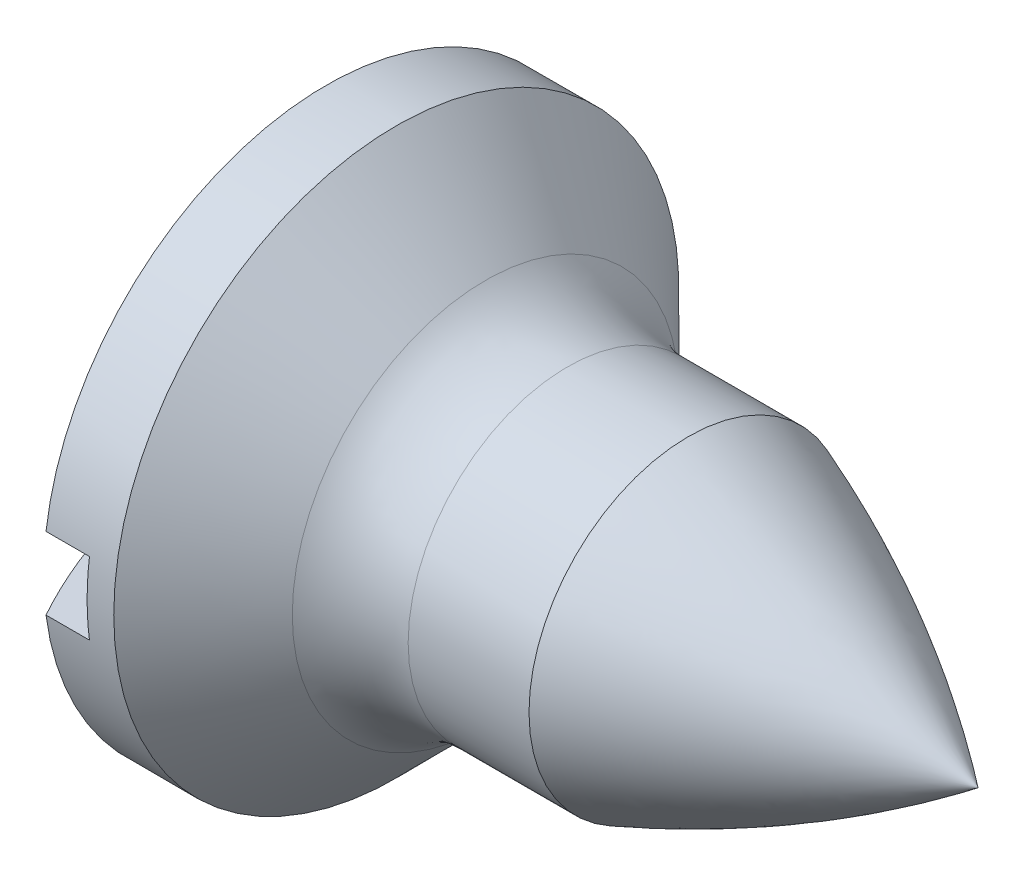
SolidWorks part; units mm, degrees
ref_plane "Front" through (0, 0, 0) normal (0, 0, 1) x (1, 0, 0)
ref_plane "Top" through (0, 0, 0) normal (0, 1, 0) x (1, 0, 0)
ref_plane "Right" through (0, 0, 0) normal (1, 0, 0) x (0, 0, -1)
sketch "Sketch1" plane through (0, 0, 0) normal (0, 0, 1) x (1, 0, 0)
  line L0 (-40.1945, 0) -> (11.3165, 0) construction
  line L1 (5.0078, 1.1) -> (5.0078, 0)
  line L2 (5.0078, 1.1) -> (2.1735, 1.1)
  line L3 (1.6078, 1.3343) -> (0.9916, 1.9506)
  line L4 (0.9916, 1.9506) -> (0.5078, 1.9506)
  line L5 (5.0078, 0) -> (0, 0)
  line L6 (2.4078, 2.2911) -> (2.4078, -1.7726) construction
  arc A0 (0.5078, 1.9506) -> (0, 0) centre (4, 0) ccw
  arc A1 (2.1735, 1.1) -> (1.6078, 1.3343) centre (2.1735, 1.9) cw
  point P12 (0.0078, 0.25)
  dimension "D2" = 45
  dimension "l" = 4.5
  dimension "k" = 1.1
  dimension "f" = 0.5
revolve "Base" add sketch "Sketch1" angle 360 about L0
cosmetic thread "ThreadCosmetic1" [suppressed] parameters "D1"=2.6, "D2"=1.2
sketch "Sketch2" plane through (0, 0, 0) normal (0, 0, 1) x (1, 0, 0)
  line L1 (0.0078, 0.25) -> (0.8078, 0.25)
  line L3 (0.0078, -0.25) -> (0.8078, -0.25)
  line L4 (0.8078, 0.25) -> (0.8078, -0.25)
  line L5 (0.5078, 1.9506) -> (0.5078, -1.9506) construction
  line L6 (1.1738, 0) -> (-4.2219, 0) construction
  arc A0 (0.5078, 1.9506) -> (0.5078, -1.9506) centre (4, 0) ccw construction
  arc A1 (0.0078, 0.25) -> (0.0078, -0.25) centre (0.5078, 0) ccw
  dimension "n" = 0.5
  dimension "t" = 0.8
extrude "Slot" cut sketch "Sketch2" against normal through all and the other way through all
sketch "Sketch3" plane through (0, 0, 0) normal (0, 0, 1) x (1, 0, 0)
  line L0 (1.3282, 0) -> (-8.063, 0) construction
  line L1 (2.1735, -1.1) -> (5.0078, -1.1) construction
  line L2 (3.4078, -1.1) -> (4.2078, -1.1)
  line L3 (4.2078, -1.1) -> (5.0078, -0.9)
  line L6 (3.4078, -1.1) -> (3.4078, -1.6)
  line L7 (3.4078, -1.6) -> (5.0078, -1.6)
  line L8 (5.0078, -1.6) -> (5.0078, -0.9)
  line L9 (5.0078, -1.1) -> (5.0078, 1.1) construction
  point P15 (4.2078, -1.1)
  dimension "D2" = 0.8
  dimension "D4" = 0.5
revolve "Cut-Revolve1" [suppressed] cut sketch "Sketch3" angle 360 about L0
sketch "Sketch4" plane through (0, 0, 0) normal (0, 0, 1) x (1, 0, 0)
  line L0 (35.861, 0) -> (12.5324, 0) construction
  line L2 (5.0078, -1.1) -> (5.0078, 1.1) construction
  line L3 (5.0078, 0) -> (3.0078, -1.1) construction
  line L6 (5.0078, 0) -> (5.5078, 0)
  line L7 (3.0078, -1.1) -> (5.0078, -1.1)
  line L8 (5.5078, 0) -> (5.5078, -1.1)
  line L9 (5.5078, -1.1) -> (5.0078, -1.1)
  arc A0 (5.0078, 0) -> (3.0078, -1.1) centre (0.1919, 6.388) cw
  dimension "D1" = 8
  dimension "D3" = 2.2
  dimension "D2" = 0.5
revolve "Cut-Revolve6" cut sketch "Sketch4" angle 360 about L0
sketch "Sketch5" plane through (0, 0, 0) normal (0, 0, 1) x (1, 0, 0)
  line L0 (2.1578, 1.6) -> (2.6578, 1.6)
  line L1 (2.6578, 1.6) -> (2.6578, 1.1)
  line L2 (2.6578, 1.1) -> (2.4078, 0.667)
  line L3 (2.4078, 0.667) -> (2.1578, 1.1)
  line L4 (2.1578, 1.1) -> (2.1578, 1.6)
  line L5 (0, 0) -> (0.2368, 0) construction
  dimension "D2" = 0.8
  dimension "D1" = 2.2
  dimension "D3" = 0.5
revolve "Cut-Revolve10" [suppressed] cut sketch "Sketch5" angle 360 about L5
pattern_linear "LPattern10" [suppressed] count 4 spacing 0.6 along (1, 0, 0) of bodies 107
equation "\"D3@Sketch3\" = \"yf@Sketch3\" / 8"
equation "\"D2@ThreadCosmetic1\" = \"st@Sketch1\" - 1"
equation "\"D1@Sketch4\" = \"yc@Sketch4\" * 4"
equation "\"D3@Sketch4\" = \"st@Sketch1\""
equation "\"D2@Sketch3\" = \"yf@Sketch3\" / 2"
equation "\"D1@ThreadCosmetic1\" = \"l@Sketch1\" - \"k@Sketch1\" - \"a@Sketch1\""
equation "\"D1@Sketch5\" = \"st@Sketch1\""
equation "\"D2@Sketch5\" = \"a@Sketch1\""
equation "\"D3@Sketch5\" =  ( \"st@Sketch1\" - \"D2@ThreadCosmetic1\" )  / 2"
equation "\"D3@LPattern10\" = \"D3@Sketch5\" * 1.2"
equation "\"D1@LPattern10\" = \"D1@ThreadCosmetic1\" / \"D3@LPattern10\""
